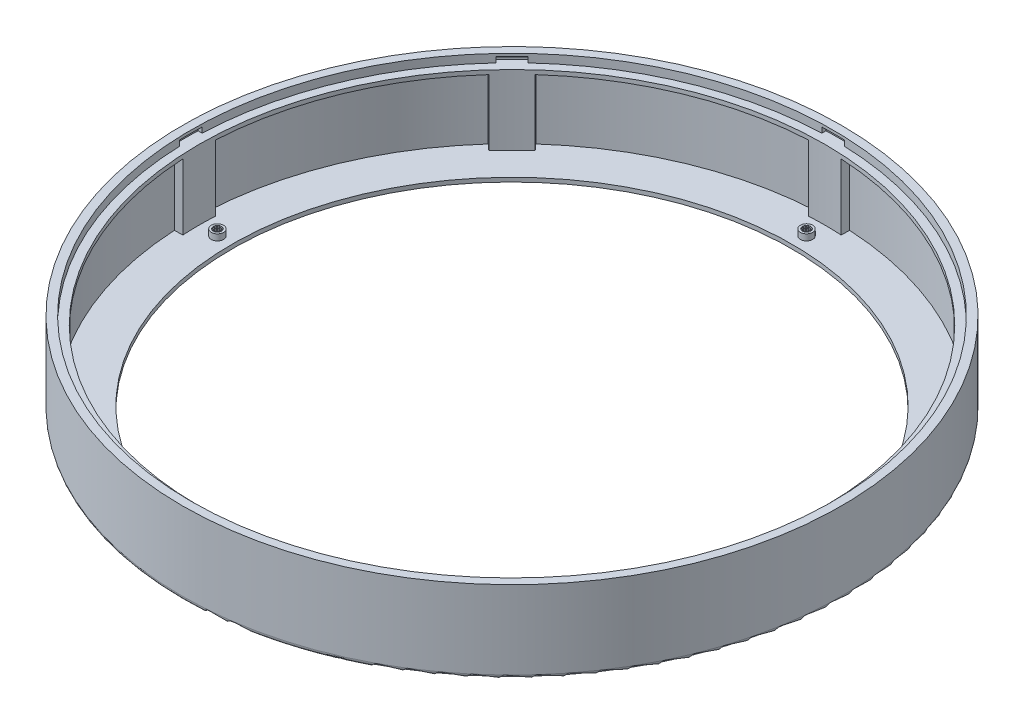
SolidWorks part; units mm, degrees
note: The reader was unsure of these and kept them because the rebuilt part matched: shared geometry of "Sketch7<3>".
ref_plane "Front Plane" through (0, 0, 0) normal (0, 0, 1) x (1, 0, 0)
ref_plane "Top Plane" through (0, 0, 0) normal (0, 1, 0) x (1, 0, 0)
ref_plane "Right Plane" through (0, 0, 0) normal (1, 0, 0) x (0, 0, -1)
sketch "Sketch1" plane through (0, 0, 0) normal (0, 0, 1) x (1, 0, 0)
  line L0 (-7.6701, 0) -> (193.172, 0) construction
  line L1 (0, 27.7946) -> (0, -16.8125) construction
  line L2 (68, 1) -> (68, 0)
  line L3 (68, 0) -> (80, 0)
  line L4 (80, 0) -> (80, 20)
  line L5 (80, 20) -> (78, 20)
  line L6 (78, 20) -> (78, 1)
  line L7 (78, 1) -> (68, 1)
  dimension "D1" = 1
  dimension "D2" = 2
  dimension "D3" = 20
  dimension "D4" = 10
  dimension "D5" = 80
revolve "Revolve1" add sketch "Sketch1" angle 360 about L1
sketch "Sketch2" plane through (0, 1, 0) normal (0, 1, 0) x (1, 0, 0)
  circle A1 centre (-0.0052, 71.5002) radius 1.4999
  circle A2 centre (71.5002, 0.0052) radius 1.4999
  circle A3 centre (0.0052, -71.5002) radius 1.4999
  circle A4 centre (-71.5002, -0.0052) radius 1.4999
  dimension "D1" = 4
extrude "Boss-Extrude2" add sketch "Sketch2" along normal blind 1.5
ref_plane "Plane2" through (0, 18, 0) normal (0, 1, 0) x (1, 0, 0)
sketch "Sketch3" plane through (0, 18, 0) normal (0, 1, 0) x (1, 0, 0)
  circle A0 centre (0, 0) radius 78
  circle A1 centre (0, 0) radius 76
  dimension "D1" = 152
  dimension "D2" = 156
extrude "Boss-Extrude3" add sketch "Sketch3" against normal blind 1
sketch "Sketch4" plane through (0, 18, 0) normal (0, 1, 0) x (1, 0, 0)
  line L0 (0, 0) -> (0, 154.2958) construction
  line L1 (-3.9775, 75.8958) -> (-4.0822, 77.8931)
  line L2 (3.9775, 75.8958) -> (4.0822, 77.8931)
  line L3 (56.479, 50.8539) -> (57.9653, 52.1922)
  line L4 (50.8539, 56.479) -> (52.1922, 57.9653)
  line L5 (75.8958, -3.9775) -> (77.8931, -4.0822)
  line L6 (75.8958, 3.9775) -> (77.8931, 4.0822)
  line L7 (50.8539, -56.479) -> (52.1922, -57.9653)
  line L8 (56.479, -50.8539) -> (57.9653, -52.1922)
  line L9 (-3.9775, -75.8958) -> (-4.0822, -77.8931)
  line L10 (3.9775, -75.8958) -> (4.0822, -77.8931)
  line L11 (-56.479, -50.8539) -> (-57.9653, -52.1922)
  line L12 (-50.8539, -56.479) -> (-52.1922, -57.9653)
  line L13 (-75.8958, 3.9775) -> (-77.8931, 4.0822)
  line L14 (-75.8958, -3.9775) -> (-77.8931, -4.0822)
  line L15 (-50.8539, 56.479) -> (-52.1922, 57.9653)
  line L16 (-56.479, 50.8539) -> (-57.9653, 52.1922)
  arc A0 (-4.0822, 77.8931) -> (4.0822, 77.8931) centre (0, 0) cw
  circle A1 centre (0, 0) radius 78 construction
  arc A2 (-3.9775, 75.8958) -> (3.9775, 75.8958) centre (0, 0) cw
  circle A3 centre (0, 0) radius 76 construction
  arc A4 (52.1922, 57.9653) -> (57.9653, 52.1922) centre (0, 0) cw
  arc A5 (50.8539, 56.479) -> (56.479, 50.8539) centre (0, 0) cw
  arc A6 (77.8931, 4.0822) -> (77.8931, -4.0822) centre (0, 0) cw
  arc A7 (75.8958, 3.9775) -> (75.8958, -3.9775) centre (0, 0) cw
  arc A8 (57.9653, -52.1922) -> (52.1922, -57.9653) centre (0, 0) cw
  arc A9 (56.479, -50.8539) -> (50.8539, -56.479) centre (0, 0) cw
  arc A10 (4.0822, -77.8931) -> (-4.0822, -77.8931) centre (0, 0) cw
  arc A11 (3.9775, -75.8958) -> (-3.9775, -75.8958) centre (0, 0) cw
  arc A12 (-52.1922, -57.9653) -> (-57.9653, -52.1922) centre (0, 0) cw
  arc A13 (-50.8539, -56.479) -> (-56.479, -50.8539) centre (0, 0) cw
  arc A14 (-77.8931, -4.0822) -> (-77.8931, 4.0822) centre (0, 0) cw
  arc A15 (-75.8958, -3.9775) -> (-75.8958, 3.9775) centre (0, 0) cw
  arc A16 (-57.9653, 52.1922) -> (-52.1922, 57.9653) centre (0, 0) cw
  arc A17 (-56.479, 50.8539) -> (-50.8539, 56.479) centre (0, 0) cw
  dimension "D1" = 3
  dimension "D2" = 3
  dimension "D3" = 8
extrude "Boss-Extrude4" add sketch "Sketch4" against normal up to surface (17 mm away) up to face at (-71.5002, 1, -1.4947)
sketch "Sketch5" plane through (0, 18, 0) normal (0, 1, 0) x (1, 0, 0)
  line L0 (0, 0) -> (0, 137.0155) construction
  line L17 (-2.7222, 77.9525) -> (-2.7571, 78.9534)
  line L18 (2.7222, 77.9525) -> (2.7571, 78.9534)
  line L19 (53.1959, 57.0456) -> (53.8789, 57.7781)
  line L20 (57.0456, 53.1959) -> (57.7781, 53.8789)
  line L21 (77.9525, 2.7222) -> (78.9534, 2.7571)
  line L22 (77.9525, -2.7222) -> (78.9534, -2.7571)
  line L23 (57.0456, -53.1959) -> (57.7781, -53.8789)
  line L24 (53.1959, -57.0456) -> (53.8789, -57.7781)
  line L25 (2.7222, -77.9525) -> (2.7571, -78.9534)
  line L26 (-2.7222, -77.9525) -> (-2.7571, -78.9534)
  line L27 (-53.1959, -57.0456) -> (-53.8789, -57.7781)
  line L28 (-57.0456, -53.1959) -> (-57.7781, -53.8789)
  line L29 (-77.9525, -2.7222) -> (-78.9534, -2.7571)
  line L30 (-77.9525, 2.7222) -> (-78.9534, 2.7571)
  line L31 (-57.0456, 53.1959) -> (-57.7781, 53.8789)
  line L32 (-53.1959, 57.0456) -> (-53.8789, 57.7781)
  arc A17 (-2.7571, 78.9534) -> (2.7571, 78.9534) centre (0, 0) cw
  arc A18 (-2.7222, 77.9525) -> (2.7222, 77.9525) centre (0, 0) cw
  circle A19 centre (0, 0) radius 78 construction
  arc A20 (53.8789, 57.7781) -> (57.7781, 53.8789) centre (0, 0) cw
  arc A21 (53.1959, 57.0456) -> (57.0456, 53.1959) centre (0, 0) cw
  arc A22 (78.9534, 2.7571) -> (78.9534, -2.7571) centre (0, 0) cw
  arc A23 (77.9525, 2.7222) -> (77.9525, -2.7222) centre (0, 0) cw
  arc A24 (57.7781, -53.8789) -> (53.8789, -57.7781) centre (0, 0) cw
  arc A25 (57.0456, -53.1959) -> (53.1959, -57.0456) centre (0, 0) cw
  arc A26 (2.7571, -78.9534) -> (-2.7571, -78.9534) centre (0, 0) cw
  arc A27 (2.7222, -77.9525) -> (-2.7222, -77.9525) centre (0, 0) cw
  arc A28 (-53.8789, -57.7781) -> (-57.7781, -53.8789) centre (0, 0) cw
  arc A29 (-53.1959, -57.0456) -> (-57.0456, -53.1959) centre (0, 0) cw
  arc A30 (-78.9534, -2.7571) -> (-78.9534, 2.7571) centre (0, 0) cw
  arc A31 (-77.9525, -2.7222) -> (-77.9525, 2.7222) centre (0, 0) cw
  arc A32 (-57.7781, 53.8789) -> (-53.8789, 57.7781) centre (0, 0) cw
  arc A33 (-57.0456, 53.1959) -> (-53.1959, 57.0456) centre (0, 0) cw
  dimension "D3" = 79.0015
  dimension "D1" = 43
  dimension "D2" = 2
  dimension "D4" = 8
extrude "Cut-Extrude1" cut sketch "Sketch5" along normal blind 1
chamfer "Chamfer1" distance 0.3 angle 45 8 edges at (78, 19, 0) (55.1543, 19, -55.1543) (0, 19, -78) (-55.1543, 19, -55.1543) (-78, 19, 0) (-55.1543, 19, 55.1543) (0, 19, 78) (55.1543, 19, 55.1543)
sketch "Sketch6" plane through (0, 2.5, 0) normal (0, 1, 0) x (1, 0, 0)
  circle A0 centre (-0.0052, 71.5002) radius 1
  circle A1 centre (71.5002, 0.0052) radius 1
  circle A2 centre (0.0052, -71.5002) radius 1
  circle A3 centre (-71.5002, -0.0052) radius 1
  dimension "D1" = 2
  dimension "D2" = 4
extrude "Cut-Extrude2" cut sketch "Sketch6" against normal up to surface (1.5 mm away) up to face at (-71.5002, 1, -1.4947)
thread "Thread1" pitch 0.3175 method extrude profile "Thread Profile1" start angle 0, offset 0, length 0, pitch 0.3175, diameter 2
ref_plane "Plane3" through (-1.0052, 2.5, -71.5002) normal (0, 0, 1) x (-1, 0, 0)
sketch "Thread Profile1" plane through (-1.0052, 2.5, -71.5002) normal (0, 0, 1) x (-1, 0, 0)
  line L0 (0, 0) -> (0, 0.3175) construction
  line L11 (0, 0) -> (0, 0.2778)
  line L12 (0, 0.2778) -> (-0.1719, 0.1786)
  line L13 (-0.1719, 0.1786) -> (-0.1719, 0.0992)
  line L15 (-0.1719, 0.0992) -> (0, 0)
  line L17 (-0.1719, 0.1389) -> (0, 0.1389) construction
  point P2 (0, 0)
  dimension "Pitch" = 0.3175
  dimension "Profile_Angle" = 60
  dimension "Profile_Land" = 0.0794
  dimension "Profile_Height" = 0.1719
thread "Thread2" pitch 0.3175 method extrude profile "Thread Profile2" start angle 0, offset 0, length 0, pitch 0.3175, diameter 2
ref_plane "Plane4" through (-72.5002, 2.5, 0.0052) normal (0, 0, 1) x (-1, 0, 0)
sketch "Thread Profile2" plane through (-72.5002, 2.5, 0.0052) normal (0, 0, 1) x (-1, 0, 0)
  line L0 (0, 0) -> (0, 0.3175) construction
  line L11 (0, 0) -> (0, 0.2778)
  line L12 (0, 0.2778) -> (-0.1719, 0.1786)
  line L13 (-0.1719, 0.1786) -> (-0.1719, 0.0992)
  line L15 (-0.1719, 0.0992) -> (0, 0)
  line L17 (-0.1719, 0.1389) -> (0, 0.1389) construction
  point P2 (0, 0)
  dimension "Pitch" = 0.3175
  dimension "Profile_Angle" = 60
  dimension "Profile_Land" = 0.0794
  dimension "Profile_Height" = 0.1719
thread "Thread3" pitch 0.3175 method extrude profile "Thread Profile4" start angle 0, offset 0, length 0, pitch 0.3175, diameter 2
ref_plane "Plane6" through (-0.9948, 2.5, 71.5002) normal (0, 0, 1) x (-1, 0, 0)
sketch "Thread Profile4" plane through (-0.9948, 2.5, 71.5002) normal (0, 0, 1) x (-1, 0, 0)
  line L0 (0, 0) -> (0, 0.3175) construction
  line L11 (0, 0) -> (0, 0.2778)
  line L12 (0, 0.2778) -> (-0.1719, 0.1786)
  line L13 (-0.1719, 0.1786) -> (-0.1719, 0.0992)
  line L15 (-0.1719, 0.0992) -> (0, 0)
  line L17 (-0.1719, 0.1389) -> (0, 0.1389) construction
  point P2 (0, 0)
  dimension "Pitch" = 0.3175
  dimension "Profile_Angle" = 60
  dimension "Profile_Land" = 0.0794
  dimension "Profile_Height" = 0.1719
thread "Thread4" pitch 0.3175 method extrude profile "Thread Profile5" start angle 0, offset 0, length 0, pitch 0.3175, diameter 2
ref_plane "Plane7" through (70.5002, 2.5, -0.0052) normal (0, 0, 1) x (-1, 0, 0)
sketch "Thread Profile5" plane through (70.5002, 2.5, -0.0052) normal (0, 0, 1) x (-1, 0, 0)
  line L0 (0, 0) -> (0, 0.3175) construction
  line L11 (0, 0) -> (0, 0.2778)
  line L12 (0, 0.2778) -> (-0.1719, 0.1786)
  line L13 (-0.1719, 0.1786) -> (-0.1719, 0.0992)
  line L15 (-0.1719, 0.0992) -> (0, 0)
  line L17 (-0.1719, 0.1389) -> (0, 0.1389) construction
  point P2 (0, 0)
  dimension "Pitch" = 0.3175
  dimension "Profile_Angle" = 60
  dimension "Profile_Land" = 0.0794
  dimension "Profile_Height" = 0.1719
fillet "Fillet1" radius 1 1 edges at (0, 0, 80)
sketch "Sketch7" plane through (0, 0, 0) normal (0, -1, 0) x (1, 0, 0)
  line L0 (27.4214, 66.4712) -> (31.7239, 76.8584) construction
  line L1 (0, 0) -> (0, 94.0506) construction
  line L6 (26.4451, 70.647) -> (31.0645, 68.7335)
  line L7 (26.4451, 70.647) -> (27.2487, 72.5871)
  line L8 (31.0645, 68.7335) -> (31.8681, 70.6737)
  line L9 (27.2487, 72.5871) -> (27.7106, 72.3958)
  line L10 (31.4062, 70.865) -> (31.8681, 70.6737)
  line L11 (31.6807, 68.4734) -> (32.6045, 68.0907)
  line L12 (31.6807, 68.4734) -> (32.4858, 70.4171)
  line L13 (32.6045, 68.0907) -> (33.4097, 70.0344)
  line L14 (32.4858, 70.4171) -> (33.4097, 70.0344)
  line L15 (24.9015, 71.2814) -> (25.7067, 73.2251)
  line L16 (26.6305, 72.8424) -> (25.7067, 73.2251)
  line L17 (25.8254, 70.8987) -> (26.6305, 72.8424)
  line L18 (25.8254, 70.8987) -> (24.9015, 71.2814)
  arc A0 (31.4062, 70.865) -> (27.7106, 72.3958) centre (29.5584, 71.6304) ccw
  circle A1 centre (0, 0) radius 79 construction
  circle M13 centre (0, 0) radius 79
  dimension "D4" = 2
  dimension "D5" = 22.5
  dimension "D7" = 70.647
  dimension "D1" = 2.5
  dimension "D2" = 0.6688
  dimension "D3" = 2.1
  dimension "D6" = 75.3894
  dimension "D8" = 1
  dimension "D9" = 2.1039
  dimension "D11" = 24.9015
extrude "Cut-Extrude3" cut sketch "Sketch7" against normal blind 3 contours L10 A0 L9 L7 L6 L8 M13 | A0 M13
extrude "Boss-Extrude5" add sketch "Sketch7<3>" against normal blind 3 contours L14 L13 L11 L12 | L16 L15 L18 L17
sketch "Sketch7<3>" plane through (0, 0, 0) normal (0, -1, 0) x (1, 0, 0) same geometry as "Sketch7"
